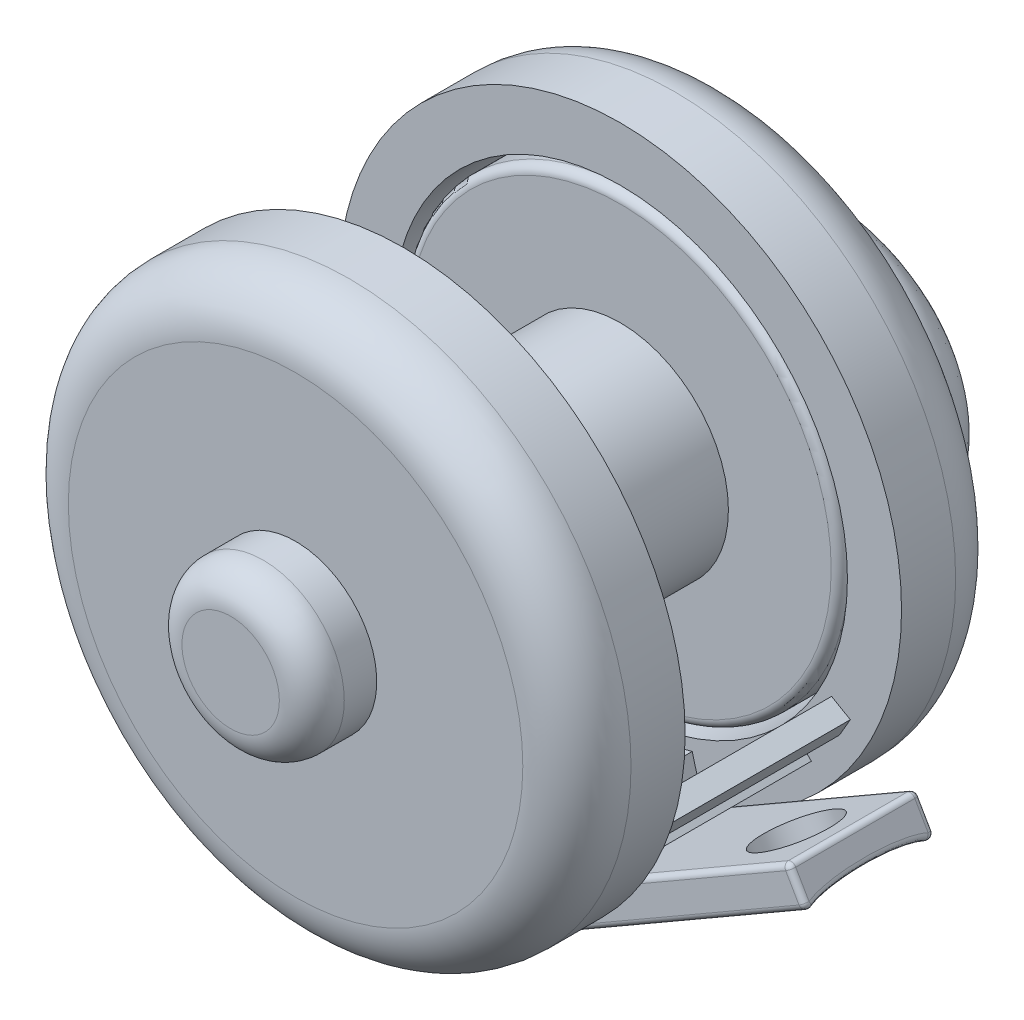
SolidWorks part; units mm, degrees
ref_plane "Front Plane" through (0, 0, 0) normal (0, 0, 1) x (1, 0, 0)
ref_plane "Top Plane" through (0, 0, 0) normal (0, 1, 0) x (1, 0, 0)
ref_plane "Right Plane" through (0, 0, 0) normal (1, 0, 0) x (0, 0, -1)
sketch "Sketch1" plane through (0, 0, 0) normal (0, 0, 1) x (1, 0, 0)
  circle A0 centre (0, 0) radius 33.02
  dimension "D1" = 66.04
extrude "Boss-Extrude1" add sketch "Sketch1" along normal blind 12.7
sketch "Sketch2" plane through (0, 0, 12.7) normal (0, 0, 1) x (1, 0, 0)
  circle A0 centre (0, 0) radius 26.67
  dimension "D1" = 53.34
extrude "Cut-Extrude1" cut sketch "Sketch2" against normal blind 11.43
sketch "Sketch3" plane through (0, 0, 1.27) normal (0, 0, 1) x (1, 0, 0)
  circle A0 centre (0, 0) radius 25.781
  dimension "D1" = 51.562
extrude "Boss-Extrude3" add sketch "Sketch3" along normal blind 11.43
sketch "Sketch4" plane through (0, 0, 12.7) normal (0, 0, 1) x (1, 0, 0)
  circle A0 centre (0, 0) radius 12.7
  dimension "D1" = 25.4
extrude "Boss-Extrude4" add sketch "Sketch4" along normal blind 25.4
sketch "Sketch5" plane through (0, 0, 38.1) normal (0, 0, 1) x (1, 0, 0)
  circle A0 centre (0, 0) radius 33.02
  dimension "D1" = 66.04
extrude "Boss-Extrude5" add sketch "Sketch5" along normal blind 12.7
sketch "Sketch7" plane through (0, 0, 38.1) normal (0, 0, -1) x (-1, 0, 0)
  circle A0 centre (0, 0) radius 33.02
  dimension "D1" = 66.04
sketch "Sketch9" plane through (0, 0, 38.1) normal (0, 0, -1) x (-1, 0, 0)
  circle A0 centre (0, 0) radius 26.67
  dimension "D1" = 53.34
extrude "Cut-Extrude4" cut sketch "Sketch9" against normal blind 11.43
sketch "Sketch10" plane through (0, 0, 38.1) normal (0, 0, -1) x (-1, 0, 0)
  circle A0 centre (0, 0) radius 25.781
  dimension "D1" = 51.562
extrude "Boss-Extrude8" add sketch "Sketch10" against normal blind 11.43
fillet "Fillet1" radius 1.016 2 edges at (-25.781, 0, 38.1) (25.781, 0, 12.7)
fillet "Fillet2" radius 6.35 1 edges at (33.02, 0, 0) type face fillet first side face at (33.02, 0, 0) second side face at (33.02, 0, 12.7)
fillet "Fillet3" radius 6.35 1 edges at (33.02, 0, 50.8) type face fillet first side face at (33.02, 0, 50.8) second side face at (33.02, 0, 50.8)
sketch "Sketch11" plane through (0, 0, 50.8) normal (0, 0, 1) x (1, 0, 0)
  circle A0 centre (0, 0) radius 9.525
  dimension "D1" = 19.05
extrude "Boss-Extrude9" add sketch "Sketch11" along normal blind 7.62
fillet "Fillet4" radius 3.81 1 edges at (9.525, 0, 58.42)
sketch "Sketch12" plane through (0, 0, 0) normal (0, 0, -1) x (-1, 0, 0)
  ellipse E0 centre (0, 0) end of major axis (22.5458, -10.9778) minor radius 19.7085
extrude "Boss-Extrude10" add sketch "Sketch12" along normal blind 6.35
fillet "Fillet5" radius 3.81 1 edges at (-22.5458, -10.9778, -6.35)
sketch "Sketch14" plane through (0, 0, 38.1) normal (0, 0, -1) x (-1, 0, 0)
  line L5 (-8.4507, -26.6606) -> (-5.9973, -27.318)
  line L6 (-8.4507, -26.6606) -> (-9.1081, -29.114)
  line L11 (-9.1081, -29.114) -> (-6.6547, -29.7714)
  line L12 (-5.9973, -27.318) -> (-6.6547, -29.7714)
  line L18 (-9.1081, -29.114) -> (-6.6547, -29.7714)
  line L19 (-8.4507, -26.6606) -> (-5.9973, -27.318)
  line L22 (-8.4507, -26.6606) -> (-6.6547, -29.7714) construction
  line L23 (-9.1081, -29.114) -> (-5.9973, -27.318) construction
  line L29 (-15.0556, -23.5663) -> (-12.8559, -24.8363)
  line L30 (-1.27, -27.94) -> (1.27, -27.94)
  line L31 (-1.27, -27.94) -> (-1.27, -30.48)
  line L32 (-1.27, -30.48) -> (1.27, -30.48)
  line L33 (1.27, -27.94) -> (1.27, -30.48)
  line L34 (-1.27, -27.94) -> (1.27, -30.48) construction
  line L35 (-1.27, -30.48) -> (1.27, -27.94) construction
  line L40 (-15.0556, -23.5663) -> (-16.3256, -25.766)
  line L46 (-16.3256, -25.766) -> (-14.1259, -27.036)
  line L47 (-12.8559, -24.8363) -> (-14.1259, -27.036)
  line L49 (-16.3256, -25.766) -> (-14.1259, -27.036)
  line L50 (-15.0556, -23.5663) -> (-12.8559, -24.8363)
  line L52 (-1.27, -30.48) -> (1.27, -30.48)
  line L53 (-15.0556, -23.5663) -> (-14.1259, -27.036) construction
  line L54 (-16.3256, -25.766) -> (-12.8559, -24.8363) construction
  line L55 (-1.27, -27.94) -> (1.27, -27.94)
  line L56 (-20.6346, -18.8679) -> (-18.8385, -20.664)
  line L57 (-20.6346, -18.8679) -> (-22.4306, -20.664)
  line L58 (-22.4306, -20.664) -> (-20.6346, -22.46)
  line L59 (-18.8385, -20.664) -> (-20.6346, -22.46)
  line L60 (-22.4306, -20.664) -> (-20.6346, -22.46)
  line L61 (-20.6346, -18.8679) -> (-18.8385, -20.664)
  line L62 (-20.6346, -18.8679) -> (-20.6346, -22.46) construction
  line L63 (-22.4306, -20.664) -> (-18.8385, -20.664) construction
  line L64 (-24.8074, -12.8857) -> (-23.5374, -15.0854)
  line L65 (-24.8074, -12.8857) -> (-27.0072, -14.1557)
  line L66 (-27.0072, -14.1557) -> (-25.7372, -16.3554)
  line L67 (-23.5374, -15.0854) -> (-25.7372, -16.3554)
  line L68 (-27.0072, -14.1557) -> (-25.7372, -16.3554)
  line L69 (-24.8074, -12.8857) -> (-23.5374, -15.0854)
  line L70 (-24.8074, -12.8857) -> (-25.7372, -16.3554) construction
  line L71 (-27.0072, -14.1557) -> (-23.5374, -15.0854) construction
  point P0 (0, -29.21)
  point P4 (-7.5527, -28.216)
  point P5 (-7.5527, -28.216)
  point P11 (-14.5908, -25.3011)
  point P12 (-14.5908, -25.3011)
  point P17 (-20.6346, -20.664)
  point P18 (-20.6346, -20.664)
  point P23 (-25.2723, -14.6205)
  point P24 (-25.2723, -14.6205)
  point P29 (0, -29.21)
  point P34 (0, 0)
  dimension "D2" = 5
  dimension "D12" = 2.54
extrude "Boss-Extrude11" add sketch "Sketch14" along normal blind 25.4 contours L33 L30 L31 L32 | L47 L40 | L12 L5 L6 L11 | L59 L56 L57 L58 | L67 L64 L65 L66 region at (7.5527, -28.216, 38.1) region at (14.5908, -25.3011, 38.1) region at (0, -29.21, 38.1) region at (20.6346, -20.664, 38.1) region at (25.2723, -14.6205, 38.1)
sketch "Sketch15" plane through (15.2384, -26.3937, 0) normal (0.5, -0.866, 0) x (-0.866, -0.5, 0)
  line L1 (-28.5604, -33.02) -> (28.5896, -33.02)
  line L2 (-28.5604, -33.02) -> (-28.5604, -17.78)
  line L3 (-28.5604, -17.78) -> (28.5896, -17.78)
  line L4 (28.5896, -33.02) -> (28.5896, -17.78)
  line L5 (-28.5604, -33.02) -> (28.5896, -17.78) construction
  line L6 (-28.5604, -17.78) -> (28.5896, -33.02) construction
  line L7 (1.2846, -12.7) -> (1.2846, -38.1) construction
  point P0 (0.0146, -25.4)
  dimension "D1" = 1.27
  dimension "D2" = 15.24
  dimension "D3" = 57.15
extrude "Boss-Extrude12" add sketch "Sketch15" along normal blind 5.08
sketch "Sketch16" plane through (24.734, 14.2802, 0) normal (0.866, 0.5, 0) x (0, 0, -1)
  line L0 (-17.78, -35.5568) -> (-33.02, -35.5568) construction
  ellipse E0 centre (-25.4, -35.5568) end of major axis (-17.78, -35.5568) minor radius 1.5875
  dimension "D1" = 3.175
extrude "Cut-Extrude5" cut sketch "Sketch16" against normal through all
fillet "Fillet6" radius 0.635 14 edges at (41.2424, -14.3132, 33.02) (41.2424, -14.3132, 17.78) (39.9724, -12.1135, 25.4) (41.7187, -15.1381, 25.4) (28.149, -18.9397, 33.02) (28.149, -18.9397, 17.78) (17.7658, -30.8004, 17.78) (17.7658, -30.8004, 33.02) (2.3025, -33.8622, 33.02) (2.3025, -33.8622, 17.78) (-8.2509, -42.8882, 17.78) (-9.5209, -40.6885, 25.4) (-8.2509, -42.8882, 33.02) (-7.7747, -43.7131, 25.4)
sketch "Sketch17" plane through (15.2384, -26.3937, 0) normal (-0.5, 0.866, 0) x (0.866, 0.5, 0)
  line L0 (-28.5896, -32.385) -> (-28.5896, -18.415) construction
  line L2 (-1.2846, -33.02) -> (-27.9546, -33.02) construction
  line L3 (28.5604, -18.415) -> (28.5604, -32.385) construction
  line L6 (1.2554, -17.78) -> (27.9254, -17.78) construction
  circle A0 centre (-20.9696, -25.4) radius 4.445
  circle A1 centre (20.9404, -25.4) radius 4.445
  point P8 (-19.432, -18.415)
  point P13 (23.6716, -18.415)
  dimension "D1" = 8.89
  dimension "D2" = 8.89
  dimension "D3" = 7.62
  dimension "D4" = 7.62
  dimension "D5" = 7.62
  dimension "D6" = 7.62
extrude "Cut-Extrude6" cut sketch "Sketch17" against normal through all
